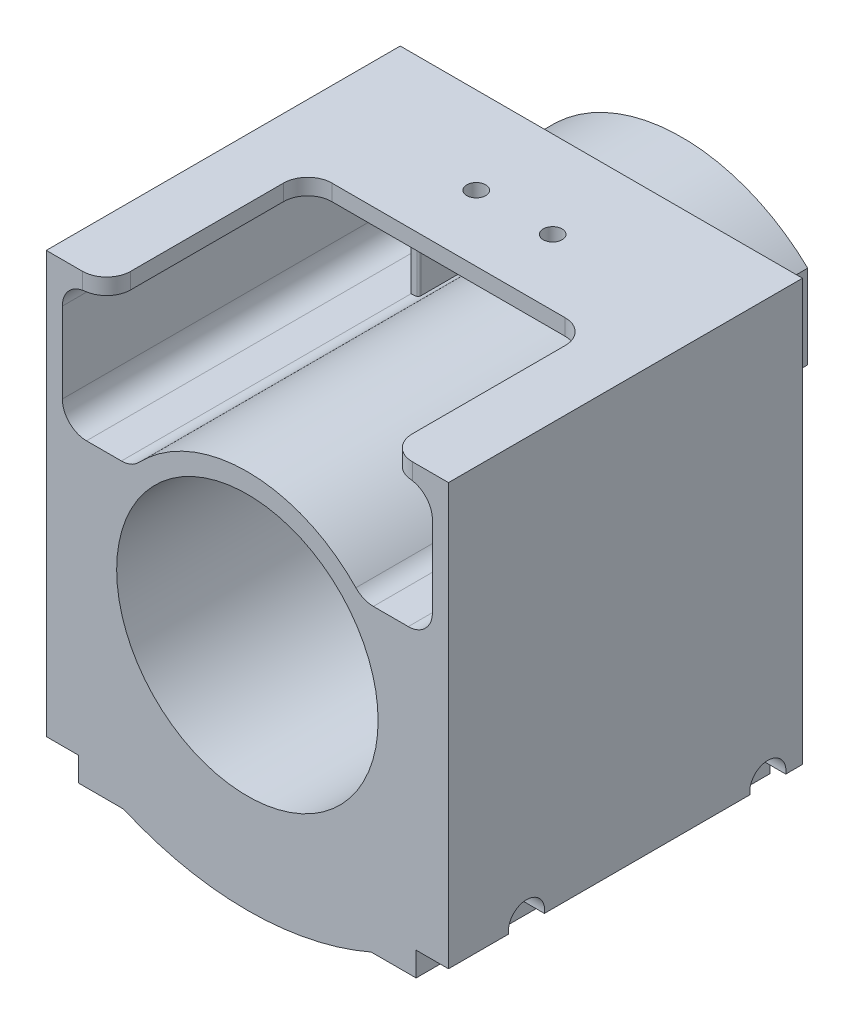
SolidWorks part; units mm, degrees
ref_plane "Front Plane" through (0, 0, 0) normal (0, 0, 1) x (1, 0, 0)
ref_plane "Top Plane" through (0, 0, 0) normal (0, 1, 0) x (1, 0, 0)
ref_plane "Right Plane" through (0, 0, 0) normal (1, 0, 0) x (0, 0, -1)
sketch "Sketch1" plane through (0, 0, 0) normal (0, 0, 1) x (1, 0, 0)
  line L1 (0, 0) -> (0, -38.55) construction
  line L2 (-25, 0) -> (-25, -29.3445)
  line L3 (25, 0) -> (25, -29.3445)
  line L4 (-25, 0) -> (-25, 20)
  line L5 (-25, 20) -> (25, 20)
  line L6 (25, 20) -> (25, 0)
  line L7 (25, -29.3445) -> (25, -32.3445)
  line L8 (25, -32.3445) -> (20.9746, -32.3445)
  line L9 (20.9746, -32.3445) -> (20.9746, -35.3445)
  line L10 (20.9746, -35.3445) -> (15.3904, -35.3445)
  line L11 (-20.9746, -35.3445) -> (-15.3904, -35.3445)
  line L12 (-20.9746, -32.3445) -> (-20.9746, -35.3445)
  line L13 (-25, -32.3445) -> (-20.9746, -32.3445)
  line L14 (-25, -29.3445) -> (-25, -32.3445)
  arc A0 (-25, -29.3445) -> (-20.9746, -32.3445) centre (0, 0) ccw construction
  arc A1 (20.9746, -32.3445) -> (25, -29.3445) centre (0, 0) ccw construction
  arc A2 (15.3904, -35.3445) -> (20.9746, -32.3445) centre (0, 0) ccw construction
  arc A3 (-15.3904, -35.3445) -> (15.3904, -35.3445) centre (0, 0) ccw
  arc A4 (-20.9746, -32.3445) -> (-15.3904, -35.3445) centre (0, 0) ccw construction
  dimension "D1" = 77.1
  dimension "D2" = 50
  dimension "D3" = 20
  dimension "D4" = 3
  dimension "D5" = 3
extrude "Boss-Extrude2" add sketch "Sketch1" along normal blind 44 from offset 6
sketch "Sketch2" plane through (0, 0, 50) normal (0, 0, 1) x (1, 0, 0)
  line L6 (0, 6.25) -> (0, -26.25) construction
  circle A0 centre (0, -10) radius 16.25
  dimension "D2" = 32.5
  dimension "D1" = 10
extrude "Cut-Extrude1" cut sketch "Sketch2" against normal through all both
sketch "Sketch4" plane through (0, 0, 50) normal (0, 0, 1) x (1, 0, 0)
  line L0 (-23, 18) -> (23, 18)
  line L3 (0, 20) -> (0, 6.25) construction
  line L4 (25, 20) -> (-25, 20) construction
  line L5 (23, 2) -> (14.3178, 2)
  line L6 (-23, 18) -> (-23, 2)
  line L7 (-23, 2) -> (-14.3178, 2)
  line L8 (-25, 20) -> (-25, -32.3445) construction
  line L9 (23, 18) -> (23, 2)
  circle A2 centre (0, -10) radius 16.25 construction
  arc A3 (14.3178, 2) -> (-14.3178, 2) centre (0, -10) ccw
  point P2 (0, 13.125)
  point P14 (0, 18)
  dimension "D1" = 37.3631
  dimension "D2" = 2
  dimension "D3" = 2
  dimension "D4" = 16
extrude "Cut-Extrude3" cut sketch "Sketch4" against normal through all
fillet "Fillet1" radius 3 6 edges at (23, 18, 28) (23, 2, 28) (14.3178, 2, 28) (-14.3178, 2, 28) (-23, 2, 28) (-23, 18, 28)
sketch "Sketch5" plane through (0, 20, 0) normal (0, 1, 0) x (1, 0, 0)
  line L0 (25, -50) -> (-25, -50) construction
  line L1 (-17.5, -50) -> (17.5, -50)
  line L2 (-17.5, -50) -> (-17.5, -25)
  line L3 (-17.5, -25) -> (17.5, -25)
  line L4 (17.5, -50) -> (17.5, -25)
  line L5 (0, 0) -> (0, -50) construction
  dimension "D1" = 35
  dimension "D2" = 25
extrude "Cut-Extrude4" cut sketch "Sketch5" against normal blind 10
fillet "Fillet2" radius 3 4 edges at (17.5, 19, 50) (17.5, 19, 25) (-17.5, 19, 25) (-17.5, 19, 50)
ref_plane "Plane1" through (0, 0, 14) normal (0, 0, 1) x (1, 0, 0)
sketch "Sketch6" plane through (0, 0, 14) normal (0, 0, 1) x (1, 0, 0)
  line L0 (0, -10) -> (0, 3) construction
  line L1 (0, -10) -> (4.4463, 2.216) construction
  circle A1 centre (0, -10) radius 16.25 construction
  circle A3 centre (0, -10) radius 9.5
  circle A8 centre (0, -10) radius 16.25
  circle A9 centre (0, -10) radius 13 construction
  circle A10 centre (4.4463, 2.216) radius 1.65
  circle A11 centre (12.216, -14.4463) radius 1.65
  circle A12 centre (-4.4463, -22.216) radius 1.65
  circle A13 centre (-12.216, -5.5537) radius 1.65
  dimension "D1" = 19
  dimension "D6" = 13
  dimension "D2" = 3.5
  dimension "D3" = 3.3
  dimension "D4" = 20
  dimension "D5" = 4
extrude "Boss-Extrude3" add sketch "Sketch6" against normal blind 5
sketch "Sketch7" plane through (0, 0, 0) normal (1, 0, 0) x (0, 0, -1)
  circle A0 centre (-40.3, -32) radius 2.25
  circle A1 centre (-10.3, -32) radius 2.25
  dimension "D3" = 4.5
  dimension "D1" = 32
  dimension "D2" = 10.3
  dimension "D4" = 30
extrude "Cut-Extrude5" cut sketch "Sketch7" against normal through all both and the other way through all
sketch "Sketch8" plane through (0, 20, 0) normal (0, 1, 0) x (1, 0, 0)
  line L0 (0, -6) -> (0, -25) construction
  line L1 (25, -6) -> (-25, -6) construction
  line L2 (14.5, -25) -> (-14.5, -25) construction
  circle A0 centre (-4.75, -16.8) radius 1.175
  circle A1 centre (4.75, -16.8) radius 1.175
  dimension "D1" = 2.35
  dimension "D2" = 9.5
  dimension "D3" = 10.8
extrude "Cut-Extrude6" cut sketch "Sketch8" against normal up to next contours A0 | A1
sketch "Sketch9" plane through (0, 0, 50) normal (0, 0, 1) x (1, 0, 0)
  line L0 (0, -28.5) -> (0, -5) construction
  line L1 (0, -10) -> (0, -28.5) construction
  line L2 (-15.6553, 2) -> (-15.6553, 11.4123)
  line L3 (15.6553, 2) -> (15.6553, 11.4123)
  line L4 (0, 8.6815) -> (0, 17.6815) construction
  line L5 (-14.6553, 2.1716) -> (-14.6553, 10.5325)
  line L6 (14.6553, 2.1716) -> (14.6553, 10.5325)
  line L7 (-15.6553, 2) -> (-15.6553, 1)
  line L8 (15.6553, 2) -> (15.6553, 1)
  line L9 (14.6553, 2) -> (14.6553, 10.9784) construction
  line L10 (-14.6553, 2) -> (-14.6553, 10.9784) construction
  arc A0 (13.4892, 2.9245) -> (-13.4892, 2.9245) centre (0, -10) ccw construction
  arc A1 (13.4892, 2.9245) -> (-13.4892, 2.9245) centre (0, -10) ccw
  arc A3 (-15.6553, 11.4123) -> (15.6553, 11.4123) centre (0, -5) cw
  arc A4 (13.4892, 2.9245) -> (15.6553, 2) centre (15.6553, 5) ccw construction
  arc A5 (-15.6553, 2) -> (-13.4892, 2.9245) centre (-15.6553, 5) ccw construction
  arc A6 (13.4892, 2.9245) -> (15.6553, 2) centre (15.6553, 5) ccw
  arc A7 (-15.6553, 2) -> (-13.4892, 2.9245) centre (-15.6553, 5) ccw
  arc A8 (12.7671, 2.2327) -> (15.6553, 1) centre (15.6553, 5) ccw
  arc A9 (12.7671, 2.2327) -> (-12.7671, 2.2327) centre (0, -10) ccw
  arc A10 (-15.6553, 1) -> (-12.7671, 2.2327) centre (-15.6553, 5) ccw
  arc A11 (-14.3156, 11.2835) -> (14.3156, 11.2835) centre (0, -5) cw
  arc A12 (-14.6553, 10.9784) -> (14.6553, 10.9784) centre (0, -5) cw construction
  arc A13 (14.6553, 10.5325) -> (14.3156, 11.2835) centre (13.6553, 10.5325) ccw
  arc A14 (-14.6553, 10.5325) -> (-14.3156, 11.2835) centre (-13.6553, 10.5325) cw
  dimension "D1" = 9
  dimension "D2" = 1
  dimension "D4" = 1
  dimension "Ring Gear Outer Dia to Center" = 23.5
  dimension "Pinion to Ring Gear Outer Diameter" = 18.5
  dimension "D3" = 1
extrude "Boss-Extrude4" add sketch "Sketch9" along normal blind 8 and the other way blind 10 from surface contours L5 A11 L6 L2 L3 A3 A6 | L7 A10 A9 A8 L8 L2 L3 A6 region at (-15.0935, 1.7255, 50) region at (-15.3051, 6.7061, 50) starting at face at (0, 7.9303, 6)
fillet "Fillet5" radius 0.25 8 edges at (14.0281, 2.4797, -4) (-14.0281, 2.4797, -4) (14.6553, 6.352, -4) (14.5664, 10.9446, -4) (-14.6553, 6.352, -4) (-14.5664, 10.9446, -4) (0, 8.6815, -4) (0, 16.6815, -4)
fillet "Fillet6" radius 0.25 5 edges at (14.6553, 6.352, 14) (14.5664, 10.9446, 14) (-14.6553, 6.352, 14) (-14.5664, 10.9446, 14) (0, 16.6815, 14)
ref_plane "Plane2" through (0, 0, 0) normal (-1, 0, 0) x (0, 0, 1)
